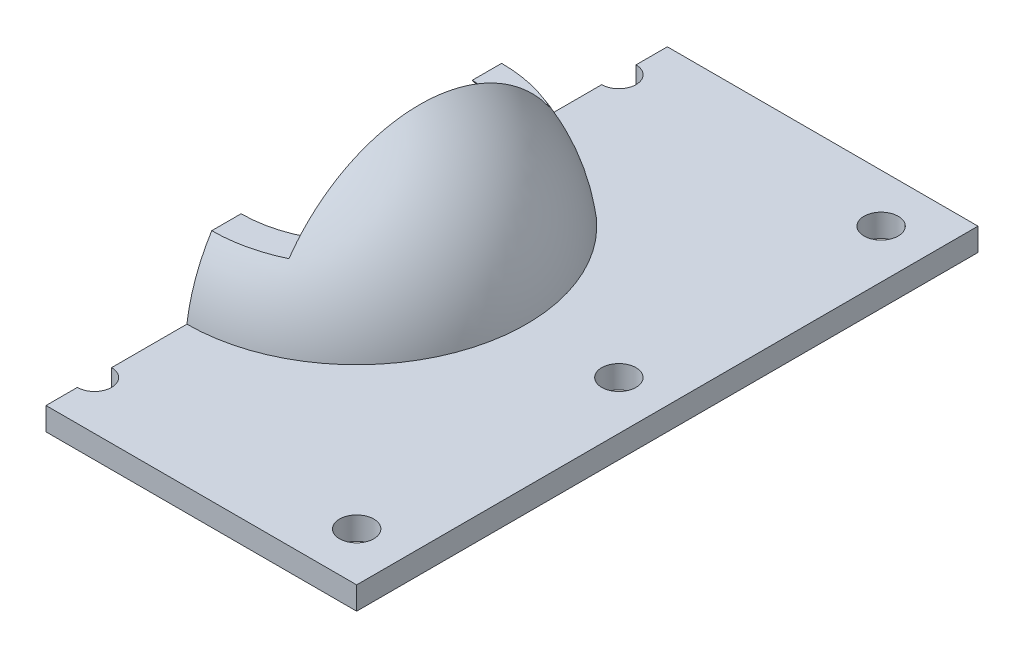
SolidWorks part; units mm, degrees
ref_plane "Front Plane" through (0, 0, 0) normal (0, 0, 1) x (1, 0, 0)
ref_plane "Top Plane" through (0, 0, 0) normal (0, 1, 0) x (1, 0, 0)
ref_plane "Right Plane" through (0, 0, 0) normal (1, 0, 0) x (0, 0, -1)
sketch "Sketch1" plane through (0, 0, 0) normal (0, 0, 1) x (1, 0, 0)
  line L0 (16.383, 0) -> (19.05, 0) construction
  line L1 (19.05, 0) -> (16.383, 0) construction
  line L2 (19.05, 0) -> (16.383, 0)
  line L3 (0, 19.05) -> (0, 16.383)
  arc A0 (19.05, 0) -> (0, 19.05) centre (0, 0) ccw
  arc A2 (16.383, 0) -> (0, 16.383) centre (0, 0) ccw
  circle A3 centre (0, 0) radius 19.05 construction
  circle A4 centre (0, 0) radius 16.383 construction
  dimension "D1" = 38.1
  dimension "D2" = 2.667
revolve "Revolve1" add sketch "Sketch1" angle 360 about L3
sketch "Sketch2" plane through (0, 0, 0) normal (0, 0, 1) x (1, 0, 0)
  line L0 (0, 10.16) -> (0, 0) construction
  line L1 (-6.985, 22.7688) -> (6.985, 22.7688)
  line L2 (-6.985, 22.7688) -> (-6.985, 10.16)
  line L3 (-6.985, 10.16) -> (6.985, 10.16)
  line L4 (6.985, 22.7688) -> (6.985, 10.16)
  dimension "D1" = 10.16
  dimension "D2" = 13.97
extrude "Cut-Extrude1" cut sketch "Sketch2" against normal mid plane 127
sketch "Sketch3" plane through (0, 0, 0) normal (0, -1, 0) x (1, 0, 0)
  line L1 (34.544, -34.544) -> (-34.544, -34.544)
  line L2 (34.544, -34.544) -> (34.544, 34.544)
  line L3 (34.544, 34.544) -> (-34.544, 34.544)
  line L4 (-34.544, -34.544) -> (-34.544, 34.544)
  line L5 (34.544, -34.544) -> (-34.544, 34.544) construction
  line L6 (34.544, 34.544) -> (-34.544, -34.544) construction
  circle A0 centre (0, 0) radius 16.51
  point P0 (0, 0)
  dimension "D2" = 33.02
  dimension "D1" = 69.088
sketch "Sketch4" plane through (0, 0, 0) normal (0, -1, 0) x (1, 0, 0)
  line L0 (34.544, -34.544) -> (-34.544, 34.544) construction
  circle A0 centre (0.1236, -0.1236) radius 16.51
  dimension "D1" = 33.02
extrude "Boss-Extrude1" add sketch "Sketch3" against normal blind 2.54
sketch "Sketch5" plane through (0, 2.54, 0) normal (0, 1, 0) x (1, 0, 0)
  line L4 (-29.1558, 29.1558) -> (-34.544, 34.544) construction
  circle A0 centre (-29.1558, 29.1558) radius 1.905
  dimension "D2" = 3.81
  dimension "D1" = 7.62
extrude "Cut-Extrude3" cut sketch "Sketch5" against normal through all contours A0
ref_plane "Plane1" through (0, 0, 0) normal (-1, 0, 0) x (0, 0, 1)
mirror "Mirror1" about plane through (0, 0, 0) normal (-1, 0, 0) of "Cut-Extrude3"
ref_plane "Plane2" through (0, 0, 0) normal (0, 0, 1) x (1, 0, 0)
sketch "Sketch8" plane through (0, 2.54, 0) normal (0, 1, 0) x (1, 0, 0)
  line L0 (-31.0608, 29.1558) -> (31.0608, 29.1558) construction
  circle A0 centre (-29.1558, 29.1558) radius 1.905 construction
  circle A1 centre (29.1558, 29.1558) radius 1.905 construction
  circle A2 centre (0, 29.1558) radius 1.905
  dimension "D1" = 3.81
extrude "Cut-Extrude5" cut sketch "Sketch8" against normal through all
mirror "Mirror2" about plane through (0, 0, 0) normal (0, 0, 1) of "Cut-Extrude5", "Cut-Extrude3", "Mirror1"
sketch "Sketch9" plane through (0, 2.54, 0) normal (0, 1, 0) x (1, 0, 0)
  line L0 (-29.1558, 31.0608) -> (-29.1558, -31.0608) construction
  circle A0 centre (-29.1558, 29.1558) radius 1.905 construction
  circle A1 centre (-29.1558, -29.1558) radius 1.905 construction
  circle A2 centre (-29.1558, 0) radius 1.905
  dimension "D1" = 3.81
extrude "Cut-Extrude6" cut sketch "Sketch9" against normal blind 2.54
mirror "Mirror3" about plane through (0, 0, 0) normal (-1, 0, 0) of "Cut-Extrude6"
sketch "Sketch7" plane through (-34.544, 0, 0) normal (-1, 0, 0) x (0, 0, 1)
  line L1 (40.4714, -2.6409) -> (-39.3684, -2.6409)
  line L2 (40.4714, -2.6409) -> (40.4714, 22.1646)
  line L3 (40.4714, 22.1646) -> (-39.3684, 22.1646)
  line L4 (-39.3684, -2.6409) -> (-39.3684, 22.1646)
extrude "Cut-Extrude4" cut sketch "Sketch7" against normal up to surface (34.544 mm away) up to plane "Plane1"
